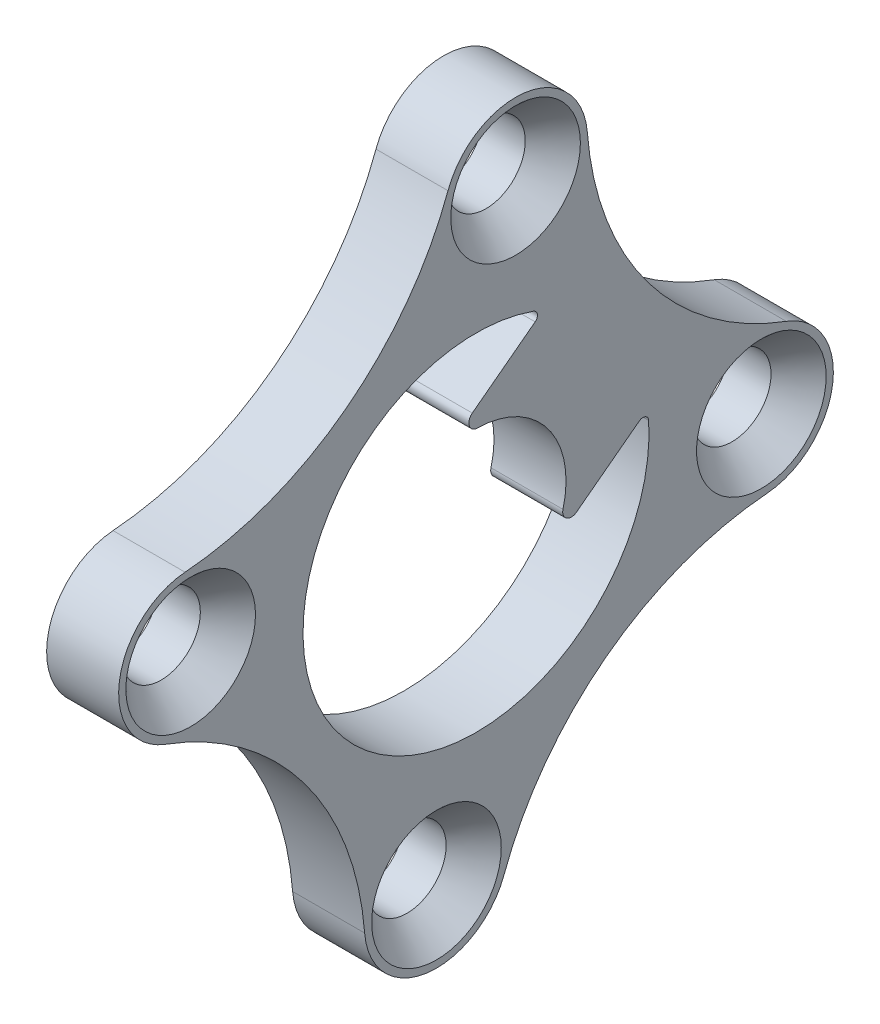
SolidWorks part; units mm, degrees
material "6061-T6 (SS)"
ref_plane "Front Plane" through (0, 0, 0) normal (0, 0, 1) x (1, 0, 0)
ref_plane "Top Plane" through (0, 0, 0) normal (0, 1, 0) x (1, 0, 0)
ref_plane "Right Plane" through (0, 0, 0) normal (1, 0, 0) x (0, 0, -1)
sketch "Sketch1" plane through (-42.315, 0, 0) normal (-1, 0, 0) x (0, 0, 1)
  line L0 (-2.6076, 6.7499) -> (0.1642, 4.6531)
  line L1 (-3.9564, 7.7703) -> (-2.4857, 6.6578) construction
  line L2 (-4.4329, -1.4239) -> (-7.2047, 0.6729)
  line L3 (-8.5536, 1.6933) -> (-4.5775, -1.3146) construction
  line L5 (-2.4857, 6.6578) -> (1.4124, 3.7089) construction
  line L6 (12.5797, 1.744) -> (-12.5797, -1.744) construction
  line L7 (1.744, -12.5797) -> (-1.744, 12.5797) construction
  arc A0 (0.1642, 4.6531) -> (-0.0599, 3.9683) centre (-0.0656, 4.3493) cw
  arc A1 (-0.0599, 3.9683) -> (-3.8349, -1.022) centre (0, 0) ccw
  arc A2 (-3.8349, -1.022) -> (-4.4329, -1.4239) centre (-4.2031, -1.1201) cw
  circle A3 centre (0, 0) radius 3.9687 construction
  circle A4 centre (0, 0) radius 3.9687 construction
  arc A5 (-2.6076, 6.7499) -> (-2.5389, 7.192) centre (-2.4543, 6.9525) cw
  arc A8 (-2.5389, 7.192) -> (-7.6115, 0.4865) centre (0, 0) cw
  arc A9 (-7.6115, 0.4865) -> (-7.2047, 0.6729) centre (-7.358, 0.4703) cw
  circle A10 centre (0, 0) radius 15.875
  arc A11 (-7.4898, 0.3914) -> (-2.4142, 7.1008) centre (0, 0) ccw construction
  circle A12 centre (-1.744, 12.5797) radius 3.175 construction
  circle A13 centre (-1.744, 12.5797) radius 2.6924 construction
  circle A14 centre (0, 0) radius 9.525 construction
  dimension "D1" = 0.381
  dimension "D2" = 0.254
  dimension "D3" = 25.4
  dimension "D4" = 0.127
  dimension "D6" = 5.3848
  dimension "D7" = 19.05
  dimension "D5" = 45
extrude "Boss-Extrude1" add sketch "Sketch1" against normal blind 3.175
sketch "Sketch2" plane through (-42.315, 0, 0) normal (-1, 0, 0) x (0, 0, 1)
  line L0 (1.744, -12.5797) -> (-1.744, 12.5797) construction
  line L1 (-2.6076, 6.7499) -> (0.1642, 4.6531) construction
  line L2 (5.7465, 7.5963) -> (9.5774, 12.6605)
  arc A0 (-2.18, 15.7246) -> (9.5774, 12.6605) centre (0, 0) cw
  circle A1 centre (0, 0) radius 15.875 construction
  circle A3 centre (0, 0) radius 9.525 construction
  arc A5 (1.2348, 13.6782) -> (-2.18, 15.7246) centre (-1.744, 12.5797) ccw
  circle A6 centre (-1.744, 12.5797) radius 3.175 construction
  arc A7 (1.2348, 13.6782) -> (5.7465, 7.5963) centre (13.8732, 18.3391) ccw
extrude "Cut-Extrude1" cut sketch "Sketch2" against normal through all
mirror "Mirror1" about plane through (-39.14, 7.5963, 5.7465) normal (0, -0.6033, 0.7975) of "Cut-Extrude1"
pattern_circular "CirPattern2" count 4 over 360 about axis through (-42.315, 0, 0) along (-1, 0, 0) of "Cut-Extrude1", "Mirror1"
hole_wizard "CSK for #4 Flat Head Machine Screw1" positions "Sketch3" profile "Sketch4" countersink size "#4" standard "ANSI Inch" end condition up to next
sketch "Sketch3" plane through (-39.14, 0, 0) normal (1, 0, 0) x (0, 0, -1)
  point P0 (12.5797, -1.744)
  point P3 (12.5797, -1.744)
  point P6 (12.5797, -1.744)
  point P9 (12.5797, -1.744)
  point P13 (1.744, 12.5797)
  point P16 (-12.5797, 1.744)
  point P19 (-1.744, -12.5797)
sketch "Sketch4" plane through (-39.14, -1.744, -12.5797) normal (0, 1, 0) x (0, 0, -1)
  line L0 (0, 0) -> (0, 3.175)
  line L1 (0, 3.175) -> (1.7272, 3.175)
  line L2 (1.7272, 3.175) -> (1.7272, 1.3003)
  line L3 (1.7272, 1.3003) -> (2.8575, 0)
  line L5 (2.8575, 0) -> (0, 0)
  line L6 (-1.7272, 1.3003) -> (-2.8575, 0) construction
  line L11 (0, -6.35) -> (0, 107.95) construction
  dimension "Thru Hole Dia." = 3.4544
  dimension "Thru Hole Depth" = 3.175
  dimension "Near C'Sink Dia." = 5.715
  dimension "Near C'Sink Angle" = 82
